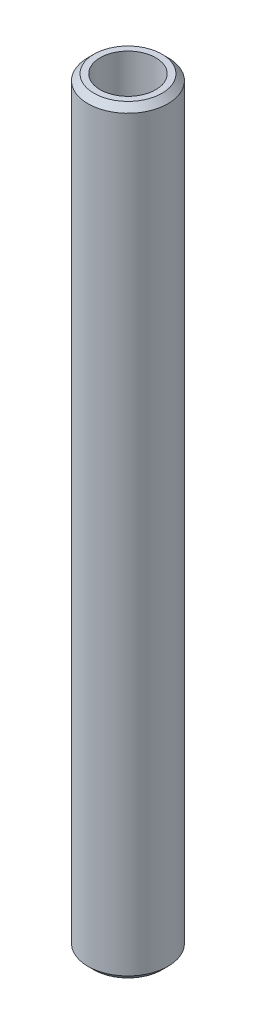
SolidWorks part; units mm, degrees
ref_plane "Front Plane" through (0, 0, 0) normal (0, 0, 1) x (1, 0, 0)
ref_plane "Top Plane" through (0, 0, 0) normal (0, 1, 0) x (1, 0, 0)
ref_plane "Right Plane" through (0, 0, 0) normal (1, 0, 0) x (0, 0, -1)
sketch "Sketch1" plane through (0, 0, 0) normal (0, 1, 0) x (1, 0, 0)
  circle A0 centre (0, 0) radius 30
  dimension "SHAFT_OD" = 60
extrude "Boss-Extrude1" add sketch "Sketch1" along normal blind 569.8611
sketch "Sketch2" plane through (0, 0, 0) normal (0, 1, 0) x (1, 0, 0)
  circle A0 centre (0, 0) radius 20.8418
  dimension "BORE_D" = 41.6835
extrude "Cut-Extrude1" cut sketch "Sketch2" along normal through all
chamfer "Chamfer1" distance 4.5188 angle 45 2 edges at (0, 569.8611, 30) (0, 0, 30)
